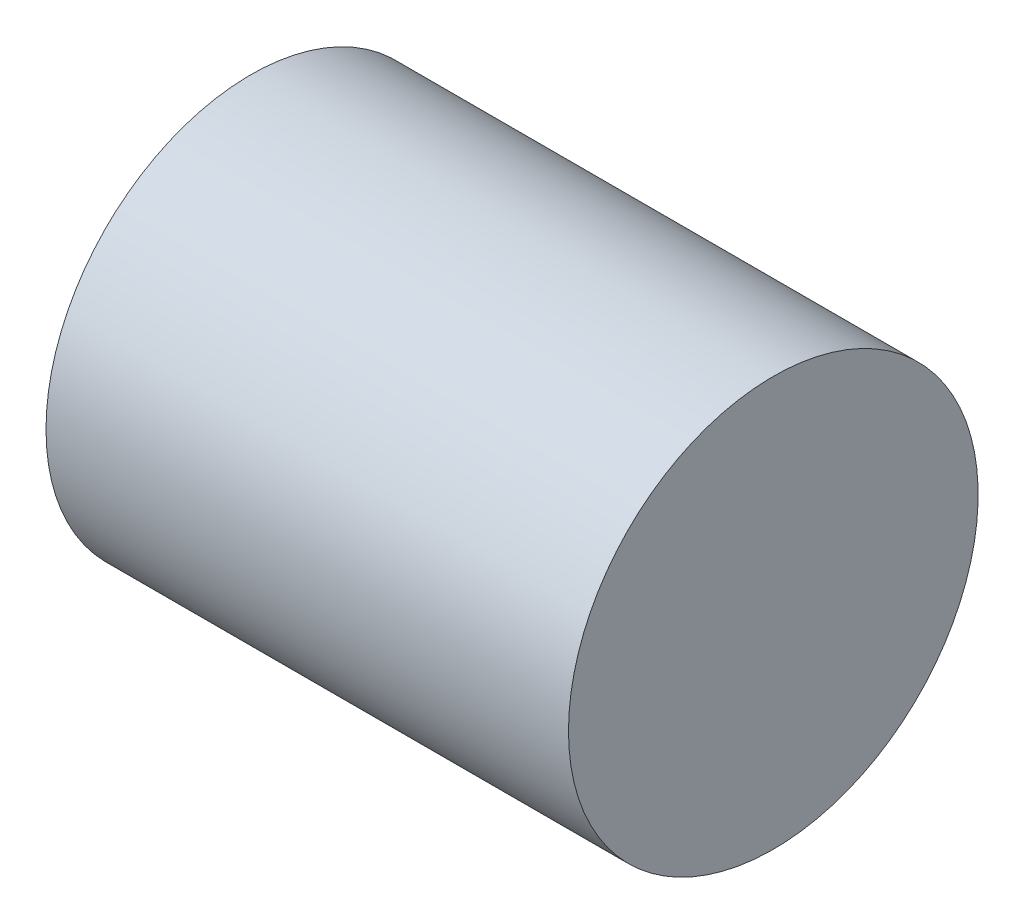
SolidWorks part; units mm, degrees
ref_plane "Front Plane" through (0, 0, 0) normal (0, 0, 1) x (1, 0, 0)
ref_plane "Top Plane" through (0, 0, 0) normal (0, 1, 0) x (1, 0, 0)
ref_plane "Right Plane" through (0, 0, 0) normal (1, 0, 0) x (0, 0, -1)
sketch "Sketch1" plane through (-22, 0, 0) normal (-1, 0, 0) x (0, 0, 1)
  circle A0 centre (-16.4895, 98.7812) radius 15.6815
extrude "Boss-Extrude1" add sketch "Sketch1" along normal blind 40
